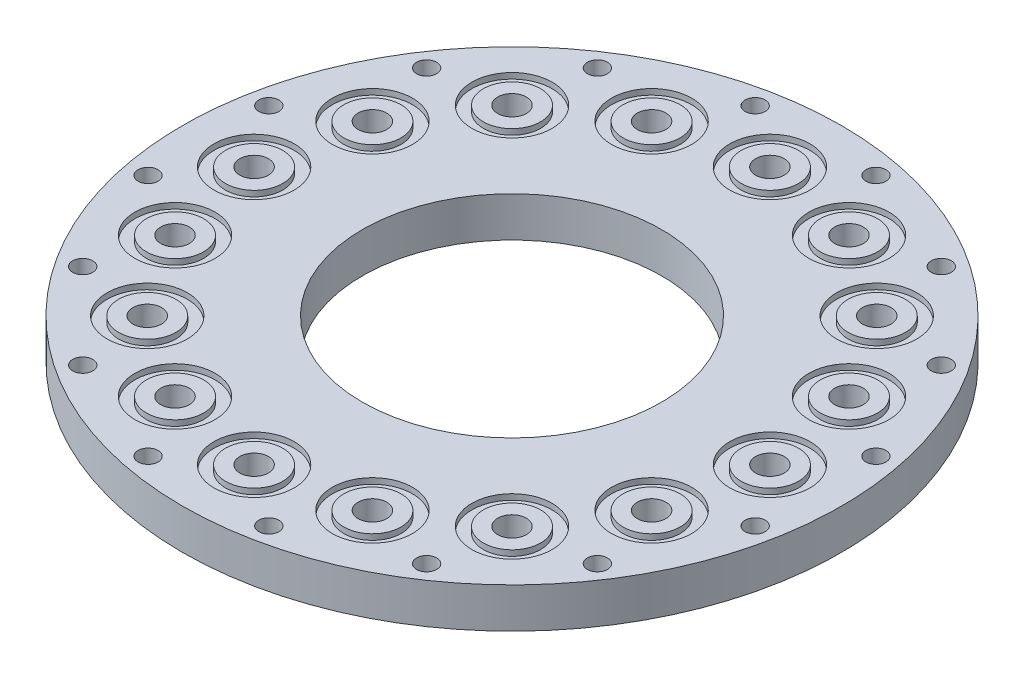
SolidWorks part; units mm, degrees
ref_plane "Front Plane" through (0, 0, 0) normal (0, 0, 1) x (1, 0, 0)
ref_plane "Top Plane" through (0, 0, 0) normal (0, 1, 0) x (1, 0, 0)
ref_plane "Right Plane" through (0, 0, 0) normal (1, 0, 0) x (0, 0, -1)
sketch "Sketch1" plane through (0, 0, 0) normal (0, 1, 0) x (1, 0, 0)
  line L0 (-10.5349, 52.9624) -> (0, 0) construction
  line L1 (0, 0) -> (62.7639, 0) construction
  line L2 (-17.2208, 41.5746) -> (0, 0) construction
  line L3 (0, 0) -> (0, 45) construction
  circle A0 centre (0, 0) radius 57.5
  circle A1 centre (0, 0) radius 54 construction
  circle A2 centre (-10.5349, 52.9624) radius 1.75
  circle A3 centre (10.5349, 52.9624) radius 1.75
  circle A4 centre (30.0008, 44.8994) radius 1.75
  circle A5 centre (44.8994, 30.0008) radius 1.75
  circle A6 centre (52.9624, 10.5349) radius 1.75
  circle A7 centre (52.9624, -10.5349) radius 1.75
  circle A8 centre (44.8994, -30.0008) radius 1.75
  circle A9 centre (30.0008, -44.8994) radius 1.75
  circle A10 centre (10.5349, -52.9624) radius 1.75
  circle A11 centre (-10.5349, -52.9624) radius 1.75
  circle A12 centre (-30.0008, -44.8994) radius 1.75
  circle A13 centre (-44.8994, -30.0008) radius 1.75
  circle A14 centre (0, 0) radius 26.1
  circle A15 centre (0, 0) radius 45 construction
  circle A16 centre (0, 45) radius 2.5
  circle A17 centre (17.2208, 41.5746) radius 2.5
  circle A18 centre (31.8198, 31.8198) radius 2.5
  circle A19 centre (41.5746, 17.2208) radius 2.5
  circle A20 centre (45, 0) radius 2.5
  circle A21 centre (41.5746, -17.2208) radius 2.5
  circle A22 centre (31.8198, -31.8198) radius 2.5
  circle A23 centre (17.2208, -41.5746) radius 2.5
  circle A24 centre (0, -45) radius 2.5
  circle A25 centre (-17.2208, -41.5746) radius 2.5
  circle A26 centre (-31.8198, -31.8198) radius 2.5
  circle A27 centre (-41.5746, -17.2208) radius 2.5
  circle A28 centre (-45, 0) radius 2.5
  circle A29 centre (-41.5746, 17.2208) radius 2.5
  circle A30 centre (-31.8198, 31.8198) radius 2.5
  circle A31 centre (-17.2208, 41.5746) radius 2.5
  circle A32 centre (-52.9624, -10.5349) radius 1.75
  circle A33 centre (-52.9624, 10.5349) radius 1.75
  circle A34 centre (-44.8994, 30.0008) radius 1.75
  circle A35 centre (-30.0008, 44.8994) radius 1.75
  point P31 (0, 0)
  point P55 (0, 0)
  dimension "D1" = 115
  dimension "D2" = 108
  dimension "D3" = 3.5
  dimension "D4" = 52.2
  dimension "D5" = 90
  dimension "D6" = 5
  dimension "D9" = 11.25
  dimension "D10" = 11.25
  dimension "D8" = 16
  dimension "D7" = 16
extrude "Boss-Extrude1" add sketch "Sketch1" along normal blind 7
sketch "Sketch2" plane through (0, 7, 0) normal (0, 1, 0) x (1, 0, 0)
  circle A0 centre (0, 0) radius 45 construction
  circle A1 centre (0, 45) radius 7
  circle A2 centre (17.2208, 41.5746) radius 7
  circle A3 centre (31.8198, 31.8198) radius 7
  circle A4 centre (41.5746, 17.2208) radius 7
  circle A5 centre (45, 0) radius 7
  circle A6 centre (41.5746, -17.2208) radius 7
  circle A7 centre (31.8198, -31.8198) radius 7
  circle A8 centre (17.2208, -41.5746) radius 7
  circle A9 centre (0, -45) radius 7
  circle A10 centre (-17.2208, -41.5746) radius 7
  circle A11 centre (-31.8198, -31.8198) radius 7
  circle A12 centre (0, 45) radius 5
  circle A13 centre (17.2208, 41.5746) radius 5
  circle A14 centre (31.8198, 31.8198) radius 5
  circle A15 centre (41.5746, 17.2208) radius 5
  circle A16 centre (45, 0) radius 5
  circle A17 centre (41.5746, -17.2208) radius 5
  circle A18 centre (31.8198, -31.8198) radius 5
  circle A19 centre (17.2208, -41.5746) radius 5
  circle A20 centre (0, -45) radius 5
  circle A21 centre (-17.2208, -41.5746) radius 5
  circle A22 centre (-31.8198, -31.8198) radius 5
  circle A23 centre (-41.5746, -17.2208) radius 5
  circle A24 centre (-45, 0) radius 5
  circle A25 centre (-41.5746, 17.2208) radius 5
  circle A26 centre (-31.8198, 31.8198) radius 5
  circle A27 centre (-17.2208, 41.5746) radius 5
  circle A28 centre (-41.5746, -17.2208) radius 7
  circle A29 centre (-45, 0) radius 7
  circle A30 centre (-41.5746, 17.2208) radius 7
  circle A31 centre (-31.8198, 31.8198) radius 7
  circle A32 centre (-17.2208, 41.5746) radius 7
  point P28 (0, 0)
  point P51 (0, 0)
  dimension "D1" = 14
  dimension "D3" = 10
  dimension "D2" = 16
  dimension "D4" = 16
extrude "Cut-Extrude1" cut sketch "Sketch2" against normal blind 1
